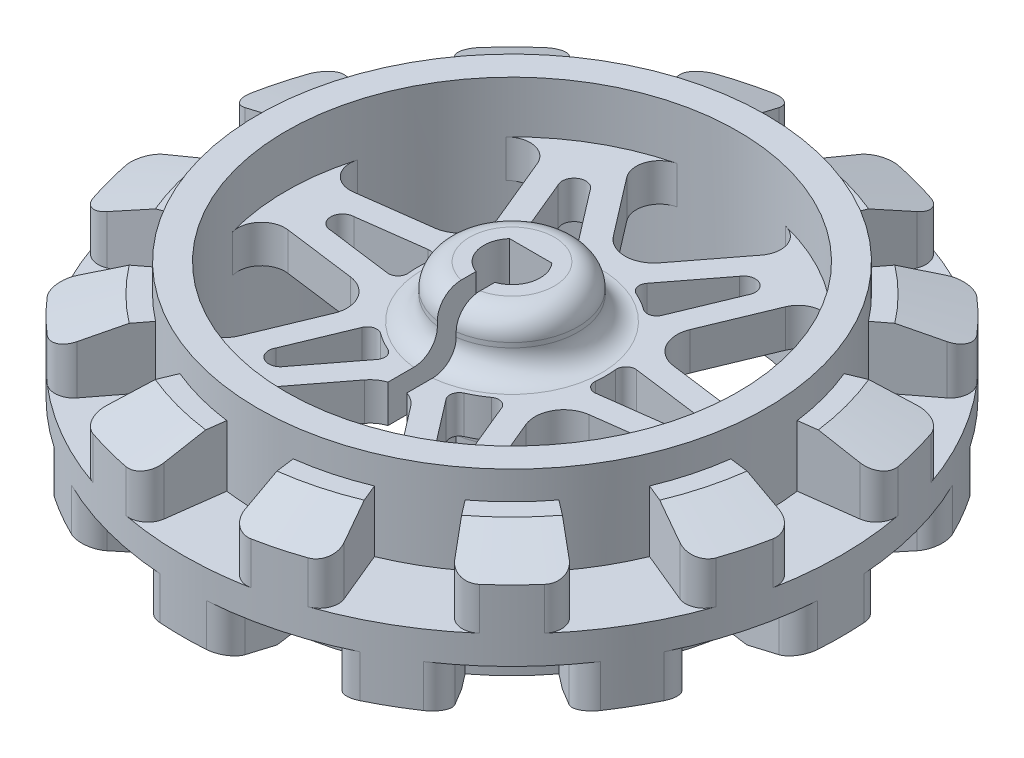
SolidWorks part; units mm, degrees
material "Custom Plastic"
ref_plane "Front Plane" through (0, 0, 0) normal (0, 0, 1) x (1, 0, 0)
ref_plane "Top Plane" through (0, 0, 0) normal (0, 1, 0) x (1, 0, 0)
ref_plane "Right Plane" through (0, 0, 0) normal (1, 0, 0) x (0, 0, -1)
ref_axis "Center" through (0, 54.4732, 0) along (0, -1, 0)
sketch "Sketch1" plane through (0, 0, 0) normal (0, 1, 0) x (1, 0, 0)
  circle A0 centre (0, 0) radius 17.5
  dimension "D1" = 35
extrude "Boss-Extrude1" add sketch "Sketch1" along normal blind 5.5 and the other way blind 5.5
sketch "Sketch3" plane through (0, 5.5, 0) normal (0, 1, 0) x (1, 0, 0)
  circle A0 centre (0, 0) radius 12
  dimension "D1" = 24
extrude "Cut-Extrude1" cut sketch "Sketch3" against normal blind 2.75
sketch "Sketch10" plane through (0, -5.5, 0) normal (0, -1, 0) x (-1, 0, 0)
  circle A0 centre (0, 0) radius 12
  dimension "D1" = 24
extrude "Cut-Extrude6" cut sketch "Sketch10" against normal blind 6.25
sketch "Sketch8" plane through (0, 5.5, 0) normal (0, 1, 0) x (1, 0, 0)
  circle A0 centre (0, 0) radius 13.5
  circle A1 centre (0, 0) radius 17.5 construction
  circle A2 centre (0, 0) radius 17.5
  dimension "D1" = 27
extrude "Cut-Extrude4" cut sketch "Sketch8" against normal blind 1.5
sketch "Sketch9" plane through (0, -5.5, 0) normal (0, -1, 0) x (-1, 0, 0)
  circle A1 centre (0, 0) radius 17.5 construction
  circle A2 centre (0, 0) radius 17.5
extrude "Cut-Extrude5" cut sketch "Sketch9" against normal blind 1.5
chamfer "Chamfer1" distance 1 distance2 3 2 edges at (0, -4, -17.5) (0, 4, 17.5) first distance on face at (0, 4, 17.5)
sketch "Sketch4" plane through (0, 5.5, 0) normal (0, 1, 0) x (1, 0, 0)
  line L0 (0, 0) -> (6.697, 16.1679) construction
  line L1 (0, 0) -> (10.6533, 13.8837) construction
  line L2 (0, 0) -> (0, 20.2479) construction
  line L3 (5.1662, 12.4724) -> (6.697, 16.1679)
  line L4 (8.2183, 10.7103) -> (10.6533, 13.8837)
  arc A0 (6.697, 16.1679) -> (10.6533, 13.8837) centre (0, 0) cw
  circle A1 centre (0, 0) radius 17.5 construction
  arc A2 (5.1662, 12.4724) -> (8.2183, 10.7103) centre (0, 0) cw
  dimension "D3" = 13.5
  dimension "D1" = 15
  dimension "D2" = 22.5
extrude "Cut-Extrude2" cut sketch "Sketch4" against normal blind 4.75
sketch "Sketch7" plane through (0, -4, 0) normal (0, -1, 0) x (-1, 0, 0)
  line L0 (0, -19.3269) -> (0, 22.3129) construction
  line L1 (0.867, -6.5858) -> (0.3792, -2.8805) construction
  line L2 (14.8043, -35.7408) -> (-22.1094, 53.3769) construction
  line L3 (-1.7621, 13.3845) -> (-2.2842, 17.3503)
  line L4 (-5.1662, 12.4724) -> (-6.697, 16.1679)
  arc A0 (-1.7621, 13.3845) -> (-5.1662, 12.4724) centre (0, 0) ccw
  arc A1 (-2.2842, 17.3503) -> (-6.697, 16.1679) centre (0, 0) ccw
  circle A3 centre (0, 0) radius 17.5 construction
  dimension "D3" = 13.5
  dimension "D1" = 7.5
  dimension "D2" = 15
extrude "Cut-Extrude3" cut sketch "Sketch7" against normal blind 3.25
fillet "Fillet1" radius 1 4 edges at (2.2842, -1.875, -17.3503) (6.697, -1.875, -16.1679) (10.6533, 1.875, -13.8837) (6.697, 1.875, -16.1679)
pattern_circular "CirPattern1" count 12 over 360 about axis through (0, 54.4732, 0) along (0, -1, 0) of "Cut-Extrude2", "Cut-Extrude3", "Fillet1"
sketch "Sketch12" plane through (0, 2.75, 0) normal (0, 1, 0) x (1, 0, 0)
  line L0 (12.967, 16.8989) -> (-11.6591, -15.1945) construction
  line L1 (-0.0202, 4.9839) -> (4.6496, 11.0696) construction
  line L2 (0, 23.3708) -> (0, -36.3574) construction
  line L3 (3.5781, 9.6733) -> (1.2219, 6.6026)
  line L4 (-3.5781, 9.6733) -> (-1.2219, 6.6026)
  line L5 (24.2999, 6) -> (-20.0267, 6) construction
  line L6 (-52.5648, 12) -> (44.1716, 12) construction
  arc A0 (4.6455, 11.0643) -> (0, 12) centre (0, 0) ccw construction
  circle A1 centre (0, 0) radius 12 construction
  arc A2 (3.5781, 9.6733) -> (2.8872, 11.6475) centre (2.5864, 10.4342) ccw
  arc A3 (1.2219, 6.6026) -> (-1.2219, 6.6026) centre (0, 7.5402) cw
  arc A4 (2.8872, 11.6475) -> (0, 12) centre (0, 0) ccw
  arc A5 (-3.5781, 9.6733) -> (-2.8872, 11.6475) centre (-2.5864, 10.4342) cw
  arc A6 (-2.8872, 11.6475) -> (0, 12) centre (0, 0) cw
  circle A7 centre (0, 0) radius 12 construction
  dimension "D1" = 37.5
  dimension "D4" = 1.25
  dimension "D3" = 6
  dimension "D2" = 3.05
extrude "Cut-Extrude7" cut sketch "Sketch12" against normal up to next
sketch "Sketch14" plane through (0, 2.75, 0) normal (0, 1, 0) x (1, 0, 0)
  line L0 (-11.1231, -19.2657) -> (8.3504, 14.4634) construction
  line L1 (0, 32.2086) -> (0, -34.7376) construction
  line L4 (3.7039, 4.2516) -> (5.0433, 7.4852)
  line L6 (1.8301, 5.3335) -> (3.9607, 8.1102)
  arc A0 (2.9472, 4.0391) -> (3.7039, 4.2516) centre (3.2419, 4.443) ccw
  arc A1 (5.0433, 7.4852) -> (3.9607, 8.1102) centre (4.5, 7.7942) ccw
  arc A2 (2.0243, 4.5719) -> (2.9472, 4.0391) centre (0, 0) cw
  arc A3 (2.0243, 4.5719) -> (1.8301, 5.3335) centre (2.2268, 5.0291) cw
  point P22 (2.5305, 4.3829)
  dimension "D4" = 3.5
  dimension "D5" = 9
  dimension "D6" = 0.5
  dimension "D3" = 5
  dimension "D7" = 0.625
  dimension "D1" = 30
  dimension "D2" = 7.5
extrude "Cut-Extrude14" cut sketch "Sketch14" against normal up to next
pattern_circular "CirPattern2" count 6 over 360 about axis through (0, 54.4732, 0) along (0, -1, 0) of "Cut-Extrude7", "Cut-Extrude14"
sketch "Sketch15" plane through (0, 2.75, 0) normal (0, 1, 0) x (1, 0, 0)
  line L0 (-0.5, -1.4142) -> (-0.5, -6.0834)
  line L1 (-1.125, 0.9922) -> (1.125, 0.9922)
  line L2 (0, 20.9425) -> (0, -30.344) construction
  line L3 (0.5, -1.4142) -> (0.5, -6.0834)
  arc A0 (-1.125, 0.9922) -> (-0.5, -1.4142) centre (0, 0) ccw
  arc A1 (1.2219, -6.6026) -> (-1.2219, -6.6026) centre (0, -7.5402) ccw construction
  arc A2 (-0.5, -6.0834) -> (0.5, -6.0834) centre (0, -7.5402) cw
  arc A3 (1.125, 0.9922) -> (0.5, -1.4142) centre (0, 0) cw
  dimension "D1" = 1.5
  dimension "D3" = 1.5
  dimension "D2" = 2.25
  dimension "D5" = 1
extrude "Cut-Extrude15" cut sketch "Sketch15" against normal up to next
sketch "Sketch16" plane through (0, 2.75, 0) normal (0, 1, 0) x (1, 0, 0)
  line L0 (-0.5, -1.4142) -> (-0.5, -6.0834) construction
  line L1 (0.5, -6.0834) -> (0.5, -1.4142) construction
  line L2 (-0.5, -3.4641) -> (-0.5, -1.4142)
  line L3 (0.5, -3.4641) -> (0.5, -1.4142)
  line L5 (1.125, 0.9922) -> (-1.125, 0.9922)
  arc A0 (-0.5, -3.4641) -> (0.5, -3.4641) centre (0, 0) cw
  arc A1 (0.5, -1.4142) -> (1.125, 0.9922) centre (0, 0) ccw construction
  arc A2 (-1.125, 0.9922) -> (-0.5, -1.4142) centre (0, 0) ccw construction
  arc A3 (0.5, -1.4142) -> (1.125, 0.9922) centre (0, 0) ccw
  arc A4 (-1.125, 0.9922) -> (-0.5, -1.4142) centre (0, 0) ccw
  dimension "D1" = 3.5
extrude "Boss-Extrude2" add sketch "Sketch16" along normal up to surface (2.75 mm away) up to face at (0, 5.5, 12)
sketch "Sketch17" plane through (0, 0.75, 0) normal (0, -1, 0) x (-1, 0, 0)
  line L0 (-0.5, -6.0834) -> (-0.5, -1.4142) construction
  line L1 (0.5, -1.4142) -> (0.5, -6.0834) construction
  line L2 (0.5, -3.4641) -> (0.5, -1.4142)
  line L3 (-1.125, 0.9922) -> (1.125, 0.9922) construction
  line L4 (-1.125, 0.9922) -> (1.125, 0.9922)
  line L5 (-0.5, -1.4142) -> (-0.5, -3.4641)
  arc A0 (-0.5, -3.4641) -> (0.5, -3.4641) centre (0, 0) cw
  arc A1 (0.5, -1.4142) -> (1.125, 0.9922) centre (0, 0) ccw construction
  arc A2 (-1.125, 0.9922) -> (-0.5, -1.4142) centre (0, 0) ccw construction
  arc A3 (0.5, -1.4142) -> (1.125, 0.9922) centre (0, 0) ccw
  arc A4 (-1.125, 0.9922) -> (-0.5, -1.4142) centre (0, 0) ccw
  dimension "D1" = 3.5
extrude "Boss-Extrude3" add sketch "Sketch17" along normal blind 3.75
fillet "Fillet2" radius 1.25 4 edges at (0, 5.5, -3.5) (0, 2.75, -3.5) (0, 0.75, -3.5) (0, -3, -3.5)
